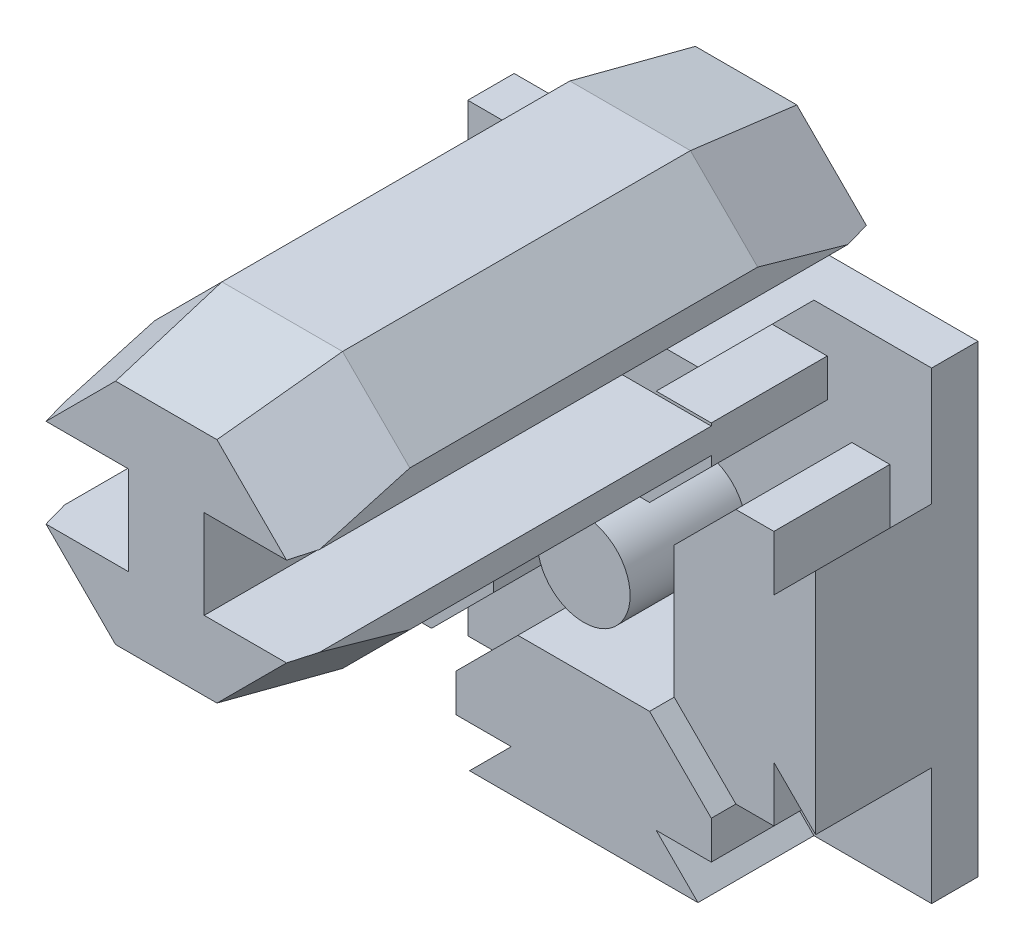
SolidWorks part; units mm, degrees
ref_plane "Front Plane" through (0, 0, 0) normal (0, 0, 1) x (1, 0, 0)
ref_plane "Top Plane" through (0, 0, 0) normal (0, 1, 0) x (1, 0, 0)
ref_plane "Right Plane" through (0, 0, 0) normal (1, 0, 0) x (0, 0, -1)
sketch "Sketch1" plane through (0, 0, 0) normal (0, 0, 1) x (1, 0, 0)
  line L0 (-4.925, 10) -> (-3.125, 8.2)
  line L1 (-10, -10) -> (10, -10)
  line L2 (-10, -10) -> (-10, 10)
  line L3 (-10, 10) -> (10, 10)
  line L4 (10, -10) -> (10, 10)
  line L5 (-10, -10) -> (10, 10) construction
  line L6 (-10, 10) -> (10, -10) construction
  line L7 (-3.125, 8.2) -> (-5.5, 8.2)
  line L8 (-5.5, 8.2) -> (-5.5, 6.5607)
  line L9 (-5.5, 6.5607) -> (-2.8393, 3.9)
  line L10 (-2.8393, 3.9) -> (2.8393, 3.9)
  line L11 (0, -55) -> (0, 55) construction
  line L12 (-10, 4.925) -> (-8.2, 3.125)
  line L13 (-8.2, 3.125) -> (-8.2, 5.5)
  line L14 (-8.2, 5.5) -> (-6.5607, 5.5)
  line L15 (-6.5607, 5.5) -> (-3.9, 2.8393)
  line L16 (-3.9, 2.8393) -> (-3.9, -2.8393)
  line L17 (55, 0) -> (-55, 0) construction
  line L18 (-4.925, -10) -> (-3.125, -8.2)
  line L19 (-3.125, -8.2) -> (-5.5, -8.2)
  line L20 (-5.5, -8.2) -> (-5.5, -6.5607)
  line L21 (-5.5, -6.5607) -> (-2.8393, -3.9)
  line L22 (-2.8393, -3.9) -> (2.8393, -3.9)
  line L23 (-6.5607, -5.5) -> (-3.9, -2.8393)
  line L24 (-8.2, -5.5) -> (-6.5607, -5.5)
  line L25 (-8.2, -3.125) -> (-8.2, -5.5)
  line L26 (-10, -4.925) -> (-8.2, -3.125)
  line L27 (4.925, -10) -> (3.125, -8.2)
  line L28 (5.5, -8.2) -> (5.5, -6.5607)
  line L29 (3.125, -8.2) -> (5.5, -8.2)
  line L30 (5.5, -6.5607) -> (2.8393, -3.9)
  line L31 (8.2, -5.5) -> (6.5607, -5.5)
  line L32 (6.5607, -5.5) -> (3.9, -2.8393)
  line L33 (8.2, -3.125) -> (8.2, -5.5)
  line L34 (10, -4.925) -> (8.2, -3.125)
  line L35 (10, 4.925) -> (8.2, 3.125)
  line L36 (8.2, 3.125) -> (8.2, 5.5)
  line L37 (8.2, 5.5) -> (6.5607, 5.5)
  line L38 (6.5607, 5.5) -> (3.9, 2.8393)
  line L39 (3.9, 2.8393) -> (3.9, -2.8393)
  line L40 (5.5, 6.5607) -> (2.8393, 3.9)
  line L41 (5.5, 8.2) -> (5.5, 6.5607)
  line L42 (3.125, 8.2) -> (5.5, 8.2)
  line L43 (4.925, 10) -> (3.125, 8.2)
  circle A0 centre (0, 0) radius 2
  point P0 (0, 0)
  point P29 (-3.9, 0)
  point P38 (0, -3.9)
  point P49 (0, 3.9)
  dimension "D2" = 4
  dimension "D1" = 20
  dimension "D3" = 3.125
  dimension "D4" = 5.5
  dimension "D5" = 45
  dimension "D6" = 4.3
  dimension "D7" = 1.8
  dimension "D8" = 1.5
  dimension "D9" = 3.125
  dimension "D10" = 5.5
  dimension "D11" = 1.8
  dimension "D12" = 4.3
extrude "Boss-Extrude1" add sketch "Sketch1" along normal blind 5 contours L43 L3 L0 L7 L8 L9 L10 L40 L41 L42 | A0 | L38 L39 L32 L31 L33 L34 L4 L35 L36 L37 | L2 L26 L25 L24 L23 L16 L15 L14 L13 L12 | L28 L30 L22 L21 L20 L19 L18 L1 L27 L29 region at (0, 7.039, 0) region at (-7.039, 0, 0) region at (7.039, 0, 0) region at (0, -7.039, 0) region at (0, 0, 0)
extrude "Boss-Extrude2" add sketch "Sketch1<3>" against normal blind 2 contours L3 L4 L1 L2
sketch "Sketch1<3>" plane through (0, 0, 0) normal (0, 0, 1) x (1, 0, 0) same geometry as "Sketch1"
sketch "Sketch2" plane through (0, 0, 5) normal (0, 0, 1) x (1, 0, 0)
  line L12 (-5.5, 6.9813) -> (-5.5, 8.0813)
  line L13 (-5.5, 8.0813) -> (1.6356, 8.0813)
  line L15 (1.6356, 11.9187) -> (-5.5, 11.9187)
  line L16 (-5.5, 11.9187) -> (-5.5, 13.0187)
  line L17 (-5.5, 13.0187) -> (-2.6, 15.9187)
  line L19 (2.6, 15.9187) -> (5.5, 13.0187)
  line L20 (5.5, 13.0187) -> (5.5, 11.9187)
  line L21 (5.5, 11.9187) -> (-1.6356, 11.9187)
  line L23 (-1.6356, 8.0813) -> (5.5, 8.0813)
  line L24 (5.5, 8.0813) -> (5.5, 6.9813)
  line L25 (5.5, 6.9813) -> (2.6, 4.0813)
  line L27 (-2.6, 4.0813) -> (-5.5, 6.9813)
  line L28 (2.6, 4.0813) -> (0, 4.0813)
  line L29 (0, -3.85) -> (0, 3.85) construction
  line L30 (0, 4.0813) -> (-2.6, 4.0813)
  line L31 (-2.6, 15.9187) -> (0, 15.9187)
  line L32 (0, 15.9187) -> (2.6, 15.9187)
  line L33 (1.6356, 11.9187) -> (1.6356, 10)
  line L34 (-4.925, 10) -> (4.925, 10) construction
  line L35 (1.6356, 10) -> (1.6356, 8.0813)
  line L36 (-1.6356, 11.9187) -> (-1.6356, 10)
  line L37 (-1.6356, 10) -> (-1.6356, 8.0813)
  line M14 (4.925, 10) -> (-4.925, 10)
  line M17 (-5.5, 8.2) -> (-5.5, 6.5607)
  line M21 (5.5, 6.5607) -> (5.5, 8.2)
  dimension "D1" = 1.1
  dimension "D2" = 4
  dimension "D3" = 5.5
  dimension "D4" = 270
extrude "Boss-Extrude3" add sketch "Sketch2" against normal blind 7 contours L32 L31 L17 L16 L15 L21 L20 L19 | L15 L36 L33 M14 region at (0, 10.9594, 5) region at (0, 13.6746, 5)
extrude "Boss-Extrude4" add sketch "Sketch2<4>" along normal blind 18 contours L30 L28 L25 L23 L13 L27 M21 M17 | L37 L13 L35 M14 | L15 L36 L33 M14 | L32 L31 L17 L16 L15 L21 L20 L19 region at (0, 6.3254, 5) region at (0, 9.0406, 5) region at (0, 10.9594, 5) region at (0, 13.6746, 5)
sketch "Sketch2<4>" plane through (0, 0, 5) normal (0, 0, 1) x (1, 0, 0) same geometry as "Sketch2"
chamfer "Chamfer1" distance 1 distance2 5 3 edges at (4.05, 14.4687, 23) (0, 15.9187, 23) (-4.05, 14.4687, 23) first distance on face at (0, 10, 23)
chamfer "Chamfer2" distance 5 distance2 1 3 edges at (4.05, 14.4687, -2) (0, 15.9187, -2) (-4.05, 14.4687, -2) first distance on face at (4.05, 14.4687, 8) first distance on face at (0, 15.9187, 8) first distance on face at (-4.05, 14.4687, 8)
chamfer "Chamfer3" distance 1 distance2 5 3 edges at (4.05, 5.5313, 23) (0, 4.0813, 23) (-4.05, 5.5313, 23) first distance on face at (0, 9.4259, 23)
